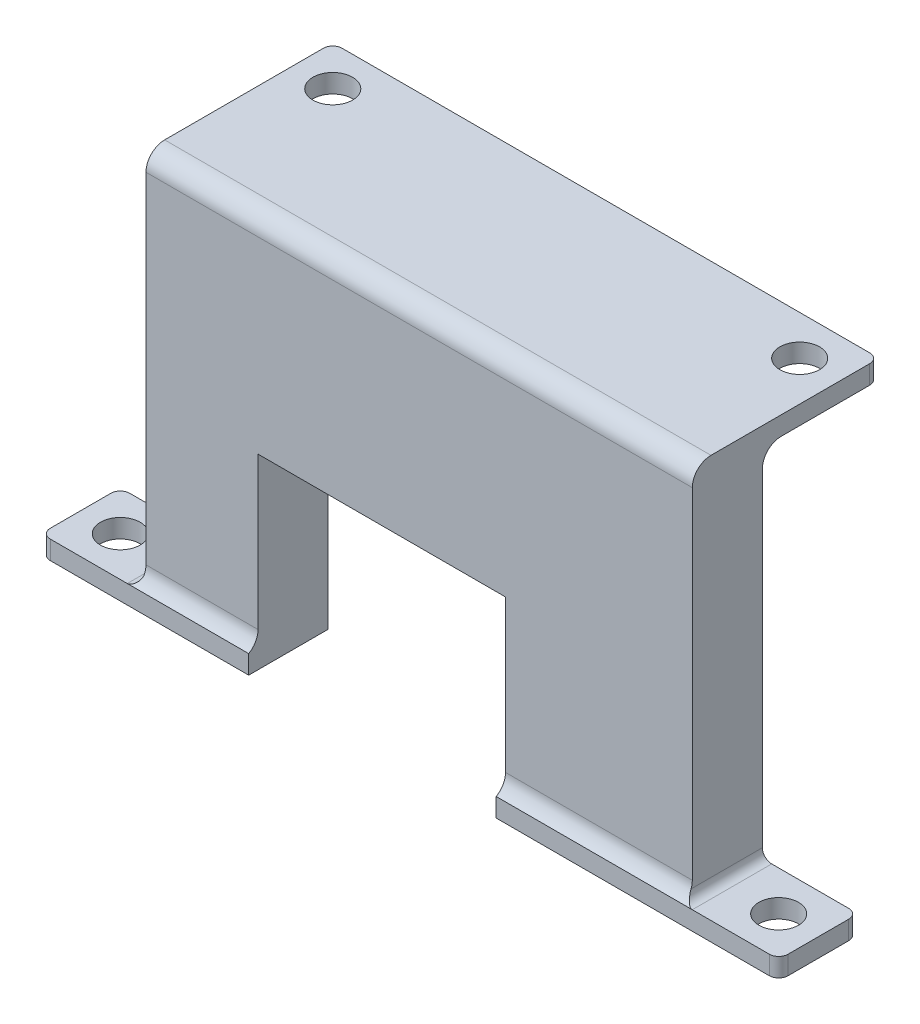
SolidWorks part; units mm, degrees
ref_plane "Front Plane" through (0, 0, 0) normal (0, 0, 1) x (1, 0, 0)
ref_plane "Top Plane" through (0, 0, 0) normal (0, 1, 0) x (1, 0, 0)
ref_plane "Right Plane" through (0, 0, 0) normal (1, 0, 0) x (0, 0, -1)
sketch "Sketch1" plane through (0, 0, 0) normal (0, 1, 0) x (1, 0, 0)
  line L0 (-79, 4.25) -> (0, 4.25) construction
  line L1 (0, 0) -> (-79, 0)
  line L2 (0, 0) -> (0, 8.5)
  line L3 (0, 8.5) -> (-79, 8.5)
  line L4 (-79, 0) -> (-79, 8.5)
  circle A0 centre (-74.75, 4.25) radius 2.125
  circle A1 centre (-4.25, 4.25) radius 2.125
  dimension "D1" = 4.25
  dimension "D4" = 70.5
  dimension "D2" = 4.25
  dimension "D3" = 4.25
  dimension "D5" = 4.25
extrude "Boss-Extrude1" add sketch "Sketch1" along normal blind 2
sketch "Sketch3" plane through (0, 2, 0) normal (0, 1, 0) x (1, 0, 0)
  line L0 (-39.5, 8.5) -> (-39.5, 0) construction
  line L1 (0, 8.5) -> (-79, 8.5) construction
  line L2 (-79, 0) -> (0, 0) construction
  line L4 (-68.75, 1) -> (-10.25, 1)
  line L5 (-68.75, 1) -> (-68.75, 8.5)
  line L6 (-68.75, 8.5) -> (-10.25, 8.5)
  line L7 (-10.25, 1) -> (-10.25, 8.5)
  line L8 (-68.75, 1) -> (-10.25, 8.5) construction
  line L9 (-68.75, 8.5) -> (-10.25, 1) construction
  point P4 (-39.5, 4.75)
  dimension "D1" = 7.5
  dimension "D2" = 58.5
extrude "Boss-Extrude2" add sketch "Sketch3" along normal blind 40.14
sketch "Sketch4" plane through (0, 0, -8.5) normal (0, 0, -1) x (-1, 0, 0)
  line L0 (68.75, 42.14) -> (68.75, 2) construction
  line L1 (10.25, 42.14) -> (68.75, 42.14)
  line L2 (10.25, 42.14) -> (10.25, 40.14)
  line L3 (10.25, 40.14) -> (68.75, 40.14)
  line L4 (68.75, 42.14) -> (68.75, 40.14)
  dimension "D1" = 2
extrude "Boss-Extrude3" add sketch "Sketch4" along normal blind 12.5
sketch "Sketch5" plane through (0, 42.14, 0) normal (0, 1, 0) x (1, 0, 0)
  line L0 (-10.25, 16.75) -> (-68.75, 16.75) construction
  line L1 (-10.25, 1) -> (-10.25, 21) construction
  line L2 (-68.75, 21) -> (-68.75, 1) construction
  line L3 (-68.75, 21) -> (-10.25, 21) construction
  circle A0 centre (-14.5, 16.75) radius 2.125
  circle A1 centre (-64.5, 16.75) radius 2.125
  dimension "D2" = 4.25
  dimension "D1" = 4.25
  dimension "D3" = 4.25
  dimension "D4" = 4.25
extrude "Cut-Extrude1" cut sketch "Sketch5" against normal up to next
fillet "Fillet1" radius 2 2 edges at (-39.5, 2, -1)
fillet "Fillet2" radius 1 6 edges at (-79, 1, 0) (-79, 1, -8.5) (-68.75, 41.14, -21) (-10.25, 41.14, -21) (0, 1, -8.5) (0, 1, 0)
fillet "Fillet3" radius 2 1 edges at (-39.5, 42.14, -1)
fillet "Fillet4" radius 1 1 edges
fillet "Fillet5" radius 1 1 edges
sketch "Sketch6" plane through (0, 0, -8.5) normal (0, 0, -1) x (-1, 0, 0)
  line L0 (1, 0) -> (78, 0) construction
  line L1 (30.25, 0) -> (56.75, 0)
  line L2 (30.25, 0) -> (30.25, 20)
  line L3 (30.25, 20) -> (56.75, 20)
  line L4 (56.75, 0) -> (56.75, 20)
  line L5 (10.25, 38.14) -> (10.25, 3) construction
  line L6 (68.75, 38.14) -> (68.75, 3) construction
  dimension "D1" = 26.5
  dimension "D2" = 20
  dimension "D3" = 20
  dimension "D4" = 12
extrude "Cut-Extrude2" cut sketch "Sketch6" against normal blind 10
